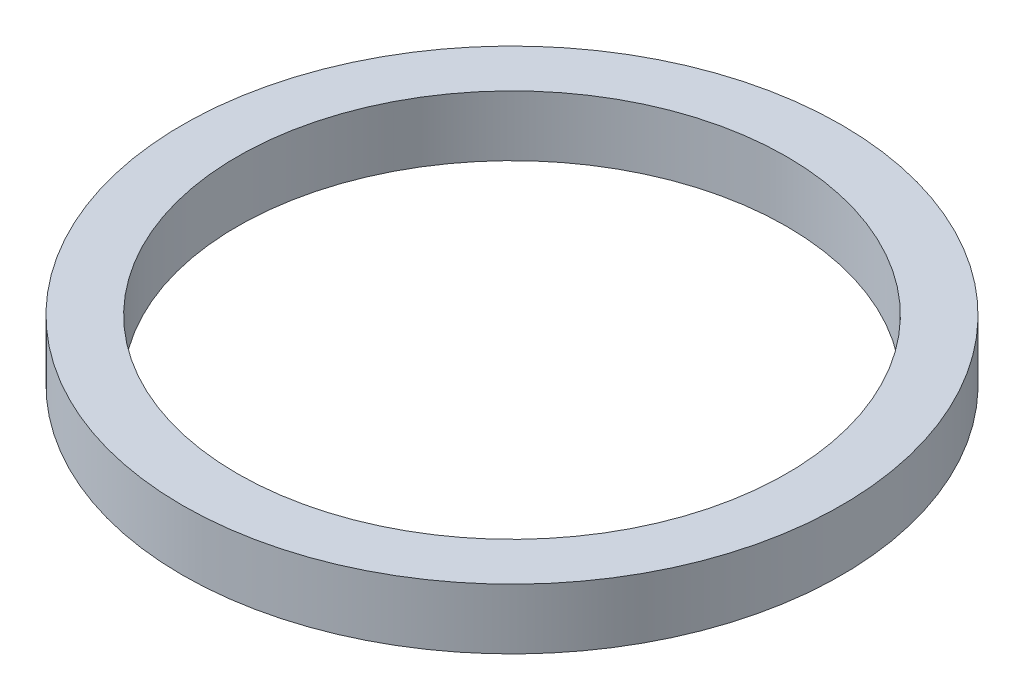
SolidWorks part; units mm, degrees
ref_plane "Front Plane" through (0, 0, 0) normal (0, 0, 1) x (1, 0, 0)
ref_plane "Top Plane" through (0, 0, 0) normal (0, 1, 0) x (1, 0, 0)
ref_plane "Right Plane" through (0, 0, 0) normal (1, 0, 0) x (0, 0, -1)
sketch "Sketch1" plane through (0, 0, 0) normal (0, 1, 0) x (1, 0, 0)
  circle A0 centre (0, 0) radius 60
  dimension "FLANGE_OD" = 120
extrude "Boss-Extrude1" add sketch "Sketch1" along normal blind 11
sketch "Sketch2" plane through (0, 0, 0) normal (0, 1, 0) x (1, 0, 0)
  circle A0 centre (0, 0) radius 50
  dimension "BORE_D" = 100
extrude "Cut-Extrude1" cut sketch "Sketch2" along normal through all
sketch "Sketch3" plane through (0, 11, 0) normal (0, 1, 0) x (1, 0, 0)
  circle A0 centre (0, 0) radius 26.6345 construction
  circle A1 centre (-26.6345, 0) radius 1.7811
  dimension "BOLT_D" = 3.5621
  dimension "BOLT_PCD" = 53.2691
extrude "Cut-Extrude2" cut sketch "Sketch3" against normal blind 8.4622 rebuild error yes
pattern_circular "CirPattern1" count 3 over 360 rebuild error yes
